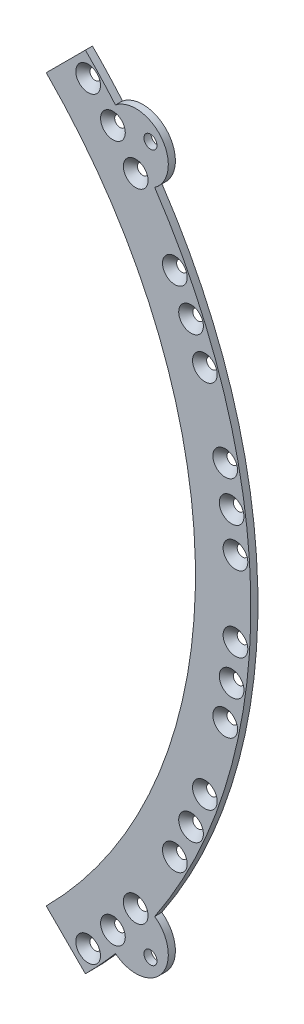
SolidWorks part; units mm, degrees
ref_plane "Front Plane" through (0, 0, 0) normal (0, 0, 1) x (1, 0, 0)
ref_plane "Top Plane" through (0, 0, 0) normal (0, 1, 0) x (1, 0, 0)
ref_plane "Right Plane" through (0, 0, 0) normal (1, 0, 0) x (0, 0, -1)
sketch "Sketch1" plane through (0, 0, 0) normal (0, 0, 1) x (1, 0, 0)
  line L0 (0, 0) -> (113.4199, -113.4199) construction
  line L1 (0, 0) -> (113.4199, 113.4199) construction
  line L2 (160.4, 0) -> (147.4, 0) construction
  line L3 (102.3184, 102.3184) -> (113.4199, 113.4199)
  line L4 (102.3184, -102.3184) -> (113.4199, -113.4199)
  line L5 (153.1288, 31.8205) -> (154.9433, 21.2965) construction
  line L6 (154.9433, 21.2965) -> (156.0354, 10.6731) construction
  line L7 (143.4518, 62.3099) -> (138.8652, 71.9542) construction
  line L8 (138.8652, 71.9542) -> (121.3212, 98.7022) construction
  line L9 (121.3212, 98.7022) -> (114.3027, 106.7513) construction
  line L10 (114.3027, 106.7513) -> (114.3027, -106.7513) construction
  line L11 (114.3027, -106.7513) -> (121.3212, -98.7022) construction
  line L12 (121.3212, -98.7022) -> (138.8652, -71.9542) construction
  line L13 (138.8652, -71.9542) -> (143.4518, -62.3099) construction
  arc A0 (0, -160.4) -> (0, 160.4) centre (0, 0) ccw construction
  circle A1 centre (121.3212, 98.7022) radius 1.5
  circle A2 centre (143.4518, 62.3099) radius 1.5
  circle A3 centre (154.9433, 21.2965) radius 1.5
  circle A4 centre (154.9433, -21.2965) radius 1.5
  circle A5 centre (143.4518, -62.3099) radius 1.5
  circle A6 centre (121.3212, -98.7022) radius 1.5
  circle A7 centre (10.6731, -156.0354) radius 1.5 construction
  circle A8 centre (31.8205, -153.1288) radius 1.5 construction
  circle A9 centre (52.3752, -147.3696) radius 1.5 construction
  circle A10 centre (90.1928, -127.7741) radius 1.5 construction
  circle A11 centre (10.6731, 156.0354) radius 1.5 construction
  circle A12 centre (31.8205, 153.1288) radius 1.5 construction
  circle A13 centre (52.3752, 147.3696) radius 1.5 construction
  circle A14 centre (90.1928, 127.7741) radius 1.5 construction
  circle A16 centre (127.7741, 90.1928) radius 1.5
  circle A17 centre (147.3696, 52.3752) radius 1.5
  circle A18 centre (153.1288, 31.8205) radius 1.5
  circle A19 centre (156.0354, 10.6731) radius 1.5
  circle A20 centre (127.7741, -90.1928) radius 1.5
  circle A21 centre (147.3696, -52.3752) radius 1.5
  circle A22 centre (153.1288, -31.8205) radius 1.5
  circle A23 centre (156.0354, -10.6731) radius 1.5
  arc A24 (113.4199, 113.4199) -> (113.4199, -113.4199) centre (0, 0) cw
  arc A25 (102.3184, 102.3184) -> (102.3184, -102.3184) centre (0, 0) cw
  arc A26 (144.6991, 0.5) -> (-144.6991, 0.5) centre (0, 0) ccw construction
  arc A27 (-144.6991, -0.5) -> (144.6991, -0.5) centre (0, 0) ccw construction
  arc A28 (110.5915, 110.5915) -> (110.5915, -110.5915) centre (0, 0) cw construction
  circle A29 centre (138.8652, 71.9542) radius 1.5
  circle A30 centre (114.3027, 106.7513) radius 1.5
  circle A31 centre (138.8652, -71.9542) radius 1.5
  circle A32 centre (114.3027, -106.7513) radius 1.5
  dimension "D3" = 3
  dimension "D1" = 45
  dimension "D2" = 45
extrude "Boss-Extrude1" add sketch "Sketch1" along normal blind 2
sketch "Sketch2" plane through (0, 0, 2) normal (0, 0, 1) x (1, 0, 0)
  line L0 (117.1059, 116.8938) -> (92.6963, 92.4842)
  line L1 (117.1059, 116.8938) -> (106.0237, 127.976)
  line L2 (92.6963, 92.4842) -> (81.6141, 103.5664)
  line L3 (106.0237, 127.976) -> (81.6141, 103.5664)
  line L4 (94.9531, -94.741) -> (127.5884, -127.3763)
  line L5 (94.9531, -94.741) -> (73.4751, -116.219)
  line L6 (127.5884, -127.3763) -> (106.1104, -148.8543)
  line L7 (73.4751, -116.219) -> (106.1104, -148.8543)
  line L8 (113.4199, 113.4199) -> (102.3184, 102.3184) construction
  line L9 (102.3184, -102.3184) -> (113.4199, -113.4199) construction
  dimension "D1" = 0.15
  dimension "D2" = 0.15
extrude "Cut-Extrude1" cut sketch "Sketch2" against normal through all
chamfer "Chamfer1" distance 2 angle 45 18 edges at (115.8027, -106.7513, 2) (122.8212, -98.7022, 2) (126.2741, -90.1928, 2) (140.3652, -71.9542, 2) (144.9518, -62.3099, 2) (145.8696, -52.3752, 2) (151.6288, -31.8205, 2) (156.4433, -21.2965, 2) (154.5354, -10.6731, 2) (154.5354, 10.6731, 2) (156.4433, 21.2965, 2) (151.6288, 31.8205, 2) (145.8696, 52.3752, 2) (144.9518, 62.3099, 2) (140.3652, 71.9542, 2) (126.2741, 90.1928, 2) (122.8212, 98.7022, 2) (115.8027, 106.7513, 2)
sketch "Sketch3" plane through (0, 0, 0) normal (0, 0, -1) x (-1, 0, 0)
  line L0 (-121.3212, 98.7022) -> (-131.917, 100.0358) construction
  line L1 (-131.917, 100.0358) -> (-127.7741, 90.1928) construction
  line L2 (-127.7741, 90.1928) -> (-121.3212, 98.7022) construction
  line L3 (-127.7741, -90.1928) -> (-121.3212, -98.7022) construction
  line L4 (-121.3212, -98.7022) -> (-131.917, -100.0358) construction
  line L5 (-131.917, -100.0358) -> (-127.7741, -90.1928) construction
  circle A0 centre (-131.917, 100.0358) radius 10.6793 construction
  circle A1 centre (-131.917, -100.0358) radius 10.6793 construction
  arc A2 (-133.1566, -89.4287) -> (-122.0376, -104.0912) centre (-131.917, -100.0358) ccw
  arc A3 (-113.5259, 113.3138) -> (-113.5259, -113.3138) centre (0, 0) ccw construction
  arc A4 (-122.0376, 104.0912) -> (-133.1566, 89.4287) centre (-131.917, 100.0358) ccw
  circle A5 centre (-131.917, 100.0358) radius 1.5 construction
  circle A6 centre (-131.917, -100.0358) radius 1.5 construction
  arc A7 (-122.0376, 104.0912) -> (-133.1566, 89.4287) centre (0, 0) ccw
  arc A8 (-122.0376, -104.0912) -> (-133.1566, -89.4287) centre (0, 0) cw
  dimension "D1" = 3
extrude "Boss-Extrude2" add sketch "Sketch3" against normal up to vertex (2 mm away) up to point (113.5259, 113.3138, 2)
sketch "Sketch4" plane through (0, 0, 0) normal (0, 0, -1) x (-1, 0, 0)
  arc A0 (-122.0376, -104.0912) -> (-133.1566, -89.4287) centre (-127.8075, -96.9195) cw
  arc A1 (-133.1566, 89.4287) -> (-122.0376, 104.0912) centre (-127.8075, 96.9195) cw
  arc A2 (-122.0376, 104.0912) -> (-133.1566, 89.4287) centre (-134.802, 102.2236) ccw
  arc A3 (-122.0376, -104.0912) -> (-133.1566, -89.4287) centre (-135.954, -103.0972) cw
  arc A4 (-113.5259, -113.3138) -> (-113.5259, 113.3138) centre (0, 0) cw construction
  arc A5 (-102.4244, 102.2122) -> (-102.4244, -102.2122) centre (0, 0) ccw construction
  point P20 (-127.5971, -97.1964)
  point P21 (-127.8075, 96.9195)
extrude "Cut-Extrude2" cut sketch "Sketch4" against normal through all
sketch "Sketch5" plane through (0, 0, 0) normal (0, 0, -1) x (-1, 0, 0)
  line L0 (-121.3212, -98.7022) -> (-131.9546, -100.0643) construction
  line L1 (-131.9546, -100.0643) -> (-127.7741, -90.1928) construction
  line L3 (-127.7741, 90.1928) -> (-131.9546, 100.0643) construction
  line L4 (-131.9546, 100.0643) -> (-121.3212, 98.7022) construction
  circle A0 centre (-131.9546, -100.0643) radius 1.85
  circle A1 centre (-131.9546, -100.0643) radius 4 construction
  arc A2 (-133.1566, -89.4287) -> (-122.0376, -104.0912) centre (-127.8075, -96.9195) ccw construction
  circle A3 centre (-131.9546, 100.0643) radius 1.85
  dimension "D1" = 3.7
  dimension "D2" = 8
extrude "Cut-Extrude3" cut sketch "Sketch5" against normal through all
